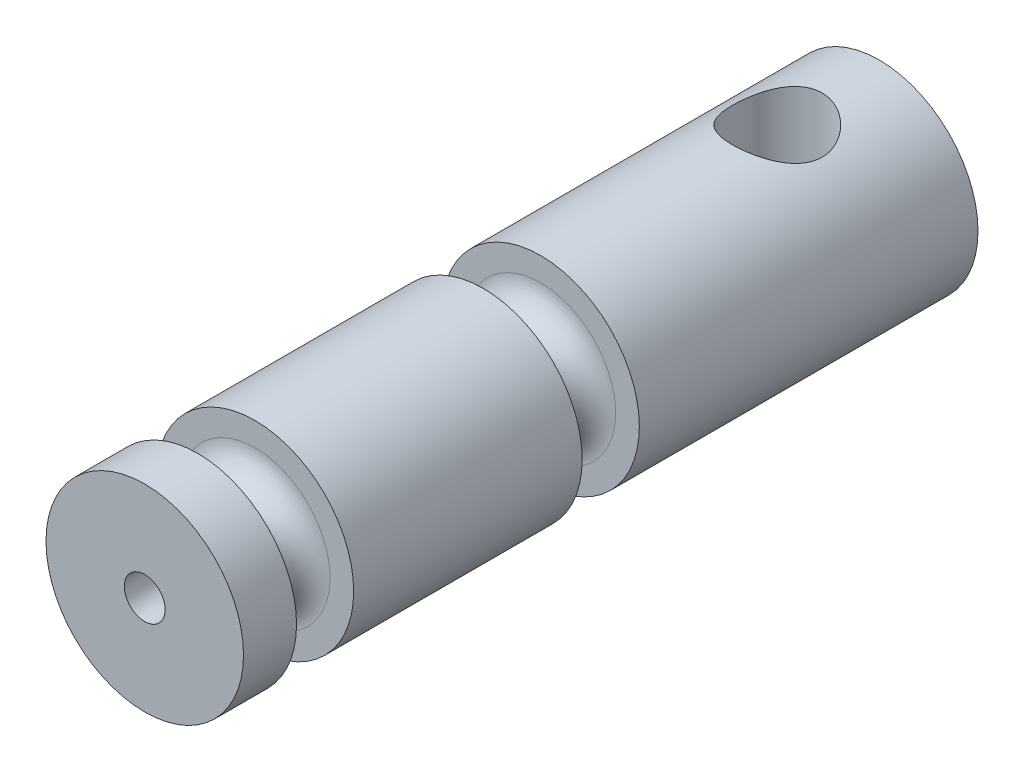
SolidWorks part; units mm, degrees
material "AISI 1015 Steel, Cold Drawn (SS)"
ref_plane "Front Plane" through (0, 0, 0) normal (0, 0, 1) x (1, 0, 0)
ref_plane "Top Plane" through (0, 0, 0) normal (0, 1, 0) x (1, 0, 0)
ref_plane "Right Plane" through (0, 0, 0) normal (1, 0, 0) x (0, 0, -1)
sketch "Sketch1" plane through (0, 0, 0) normal (0, 0, 1) x (1, 0, 0)
  circle A0 centre (0, 0) radius 3.0734
  dimension "D1" = 6.1468
extrude "Boss-Extrude1" add sketch "Sketch1" along normal blind 22.86
sketch "Sketch3" plane through (0, 0, 0) normal (0, 1, 0) x (1, 0, 0)
  circle A0 centre (0, -3.175) radius 1.397
  dimension "D1" = 2.794
  dimension "D2" = 3.175
extrude "Cut-Extrude1" cut sketch "Sketch3" against normal through all and the other way through all
sketch "Sketch4" plane through (0, 0, 0) normal (1, 0, 0) x (0, 0, -1)
  line L0 (0, 0) -> (-26.5026, 0) construction
  line L1 (-12.319, 2.3368) -> (-12.319, 3.2258)
  line L2 (-10.541, 2.3368) -> (-10.541, 3.2258)
  line L3 (-12.319, 3.2258) -> (-10.541, 3.2258)
  line L4 (-15.875, 0) -> (-15.875, 2.0116) construction
  line L5 (-19.431, 2.3368) -> (-19.431, 3.2258)
  line L6 (-19.431, 3.2258) -> (-21.209, 3.2258)
  line L7 (-21.209, 2.3368) -> (-21.209, 3.2258)
  circle A0 centre (-11.43, 2.3368) radius 0.889
  circle A1 centre (-20.32, 2.3368) radius 0.889
  dimension "D1" = 1.778
  dimension "D2" = 11.43
  dimension "D3" = 2.3368
  dimension "D4" = 4.445
revolve "Cut-Revolve1" cut sketch "Sketch4" angle 360 about L0 region at (0, 2.3368, 11.43) region at (0, 3.0272, 12.1204) region at (0, 3.0272, 10.7396) region at (0, 3.0272, 19.6296) region at (0, 2.3368, 20.32) region at (0, 3.0272, 21.0104)
sketch "Sketch6" plane through (0, 0, 0) normal (0, 0, -1) x (-1, 0, 0)
  circle A0 centre (0, 0) radius 0.635
  dimension "D1" = 1.27
extrude "Cut-Extrude2" cut sketch "Sketch6" against normal up to surface (22.86 mm away) up to face at (3.0734, 0, 22.86)
ref_plane "Plane1" through (0, 0, 11.43) normal (0, 0, 1) x (1, 0, 0)
sketch "Sketch7" plane through (0, 0, 11.43) normal (0, 0, 1) x (1, 0, 0)
  circle A0 centre (0, 0) radius 1.4478 construction
  dimension "D1" = 2.8956
ref_plane "Plane2" through (0, 0, 20.32) normal (0, 0, -1) x (-1, 0, 0)
sketch "Sketch8" plane through (0, 0, 20.32) normal (0, 0, -1) x (-1, 0, 0)
  circle A0 centre (0, 0) radius 1.4478 construction
  dimension "D1" = 2.8956
equation "\"D1@Boss-Extrude1\"=0.125+0.5 +0.1 + 0.35 -0.2+ 0.0625"
equation "\"D3@Sketch4\"=0.07/2 + 0.114/2"
